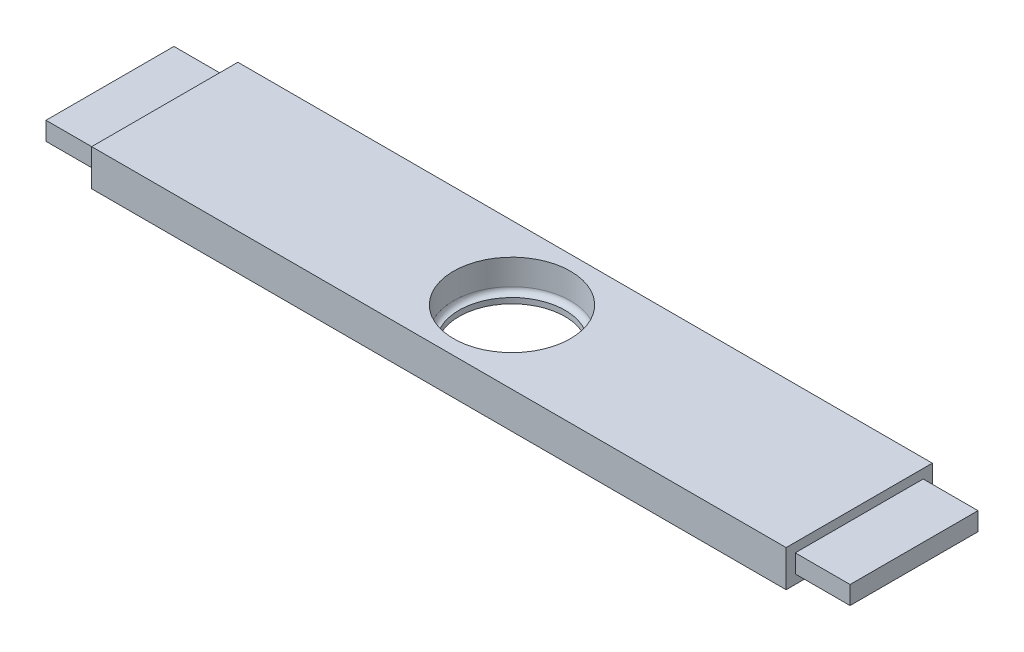
SolidWorks part; units mm, degrees
ref_plane "Front Plane" through (0, 0, 0) normal (0, 0, 1) x (1, 0, 0)
ref_plane "Top Plane" through (0, 0, 0) normal (0, 1, 0) x (1, 0, 0)
ref_plane "Right Plane" through (0, 0, 0) normal (1, 0, 0) x (0, 0, -1)
sketch "Esboço1" plane through (0, 0, 0) normal (0, 1, 0) x (1, 0, 0)
  line L1 (0, 0) -> (220, 0)
  line L2 (0, 0) -> (0, 40)
  line L3 (0, 40) -> (220, 40)
  line L4 (220, 0) -> (220, 40)
  dimension "D1" = 40
  dimension "D2" = 220
extrude "Ressalto-extrusão1" add sketch "Esboço1" along normal blind 10
sketch "Esboço2" plane through (0, 0, 0) normal (-1, 0, 0) x (0, 0, 1)
  line L0 (-40, 10) -> (-40, 0) construction
  line L1 (-2.5, 2.5) -> (-37.5, 2.5)
  line L2 (-2.5, 2.5) -> (-2.5, 7.5)
  line L3 (-2.5, 7.5) -> (-37.5, 7.5)
  line L4 (-37.5, 2.5) -> (-37.5, 7.5)
  line L6 (-40, 10) -> (0, 10) construction
  line L7 (-40, 0) -> (0, 0) construction
  line L8 (0, 10) -> (0, 0) construction
  line L9 (0, 10) -> (0, 0)
  line L10 (-40, 0) -> (0, 0)
  line L11 (-40, 10) -> (0, 10)
  line L12 (-40, 10) -> (-40, 0)
  point P4 (-20, 7.5)
  point P5 (-20, 10)
  point P7 (-37.5, 5)
  point P9 (-40, 5)
  dimension "D1" = 35
  dimension "D2" = 5
extrude "Corte-extrusão1" cut sketch "Esboço2" against normal blind 15
ref_plane "Plano1" through (110, 0, 0) normal (-1, 0, 0) x (0, 0, 1)
mirror "Espelhar1" about plane through (110, 0, 0) normal (-1, 0, 0) of "Corte-extrusão1"
sketch "Esboço3" plane through (0, 0, 0) normal (0, 1, 0) x (1, 0, 0)
  line L0 (110, 40) -> (110, 0) construction
  line L1 (205, 40) -> (15, 40) construction
  line L2 (15, 0) -> (205, 0) construction
  circle A0 centre (110, 20) radius 14.5
  dimension "D1" = 29
extrude "Corte-extrusão2" cut sketch "Esboço3" against normal through all both and the other way through all
sketch "Esboço4" plane through (0, 10, 0) normal (0, 1, 0) x (1, 0, 0)
  circle A0 centre (110, 20) radius 14.5 construction
  circle A1 centre (110, 20) radius 14.5
  circle A2 centre (110, 20) radius 16
  dimension "D1" = 1.5
extrude "Corte-extrusão3" cut sketch "Esboço4" against normal blind 8.5 and the other way through all
fillet "Filete1" radius 1.5 1 edges at (110, 1.5, -4)
